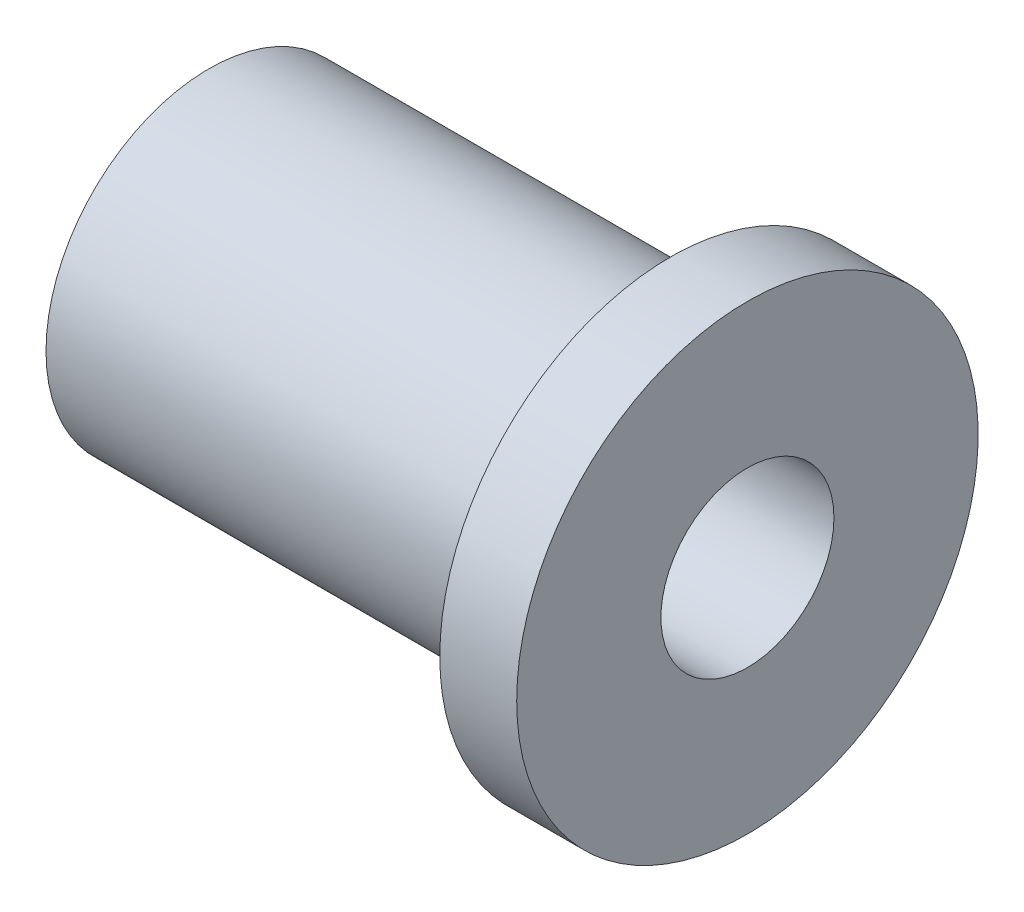
SolidWorks part; units mm, degrees
material "6061-T6 (SS)"
ref_plane "Front Plane" through (0, 0, 0) normal (0, 0, 1) x (1, 0, 0)
ref_plane "Top Plane" through (0, 0, 0) normal (0, 1, 0) x (1, 0, 0)
ref_plane "Right Plane" through (0, 0, 0) normal (1, 0, 0) x (0, 0, -1)
sketch "Sketch1" plane through (0, 0, 0) normal (0, 0, 1) x (1, 0, 0)
  line L0 (0, 0) -> (62.7055, 0) construction
  line L1 (0, 0) -> (0, 6.731)
  line L2 (0, 6.731) -> (19.05, 6.731)
  line L3 (19.05, 6.731) -> (19.05, 9.525)
  line L4 (19.05, 9.525) -> (22.225, 9.525)
  line L5 (22.225, 9.525) -> (22.225, 0)
  line L6 (22.225, 0) -> (0, 0)
  dimension "D1" = 13.462
  dimension "D2" = 3.175
  dimension "D3" = 19.05
  dimension "D4" = 19.05
revolve "Revolve1" add sketch "Sketch1" angle 360 about L0
hole_wizard "9/32 (0.28125) Diameter Hole1" positions "Sketch4" profile "Sketch5" hole size "9/32" standard "ANSI Inch" end condition through all
sketch "Sketch4" plane through (22.225, 0, 0) normal (1, 0, 0) x (0, 0, -1)
  point P0 (0, 0)
sketch "Sketch5" plane through (22.225, 0, 0) normal (0, 1, 0) x (0, 0, -1)
  line L0 (0, 0) -> (0, 22.225)
  line L1 (0, 22.225) -> (3.5719, 22.225)
  line L2 (3.5719, 22.225) -> (3.5719, 0)
  line L5 (3.5719, 0) -> (0, 0)
  line L11 (0, -6.35) -> (0, 107.95) construction
  dimension "Thru Hole Dia." = 7.1437
  dimension "Thru Hole Depth" = 22.225
hole_wizard "Pipe Tap Drill for 1/8 Tap2" positions "Sketch6" profile "Sketch8" hole size "1/8" standard "ANSI Inch"
sketch "Sketch6" plane through (0, 0, 0) normal (-1, 0, 0) x (0, 0, 1)
  point P0 (0, 0)
sketch "Sketch8" plane through (0, 0, 0) normal (0, 1, 0) x (0, 0, 1)
  line L0 (0, 0) -> (0, 15.2335)
  line L1 (0, 15.2335) -> (4.2164, 12.7)
  line L2 (4.2164, 12.7) -> (4.2164, 0)
  line L5 (4.2164, 0) -> (0, 0)
  line L10 (0, 15.2335) -> (-4.2164, 12.7) construction
  line L11 (0, -6.35) -> (0, 107.95) construction
  dimension "Hole Dia." = 8.4328
  dimension "Hole Depth" = 12.7
  dimension "Drill Angle" = 118
